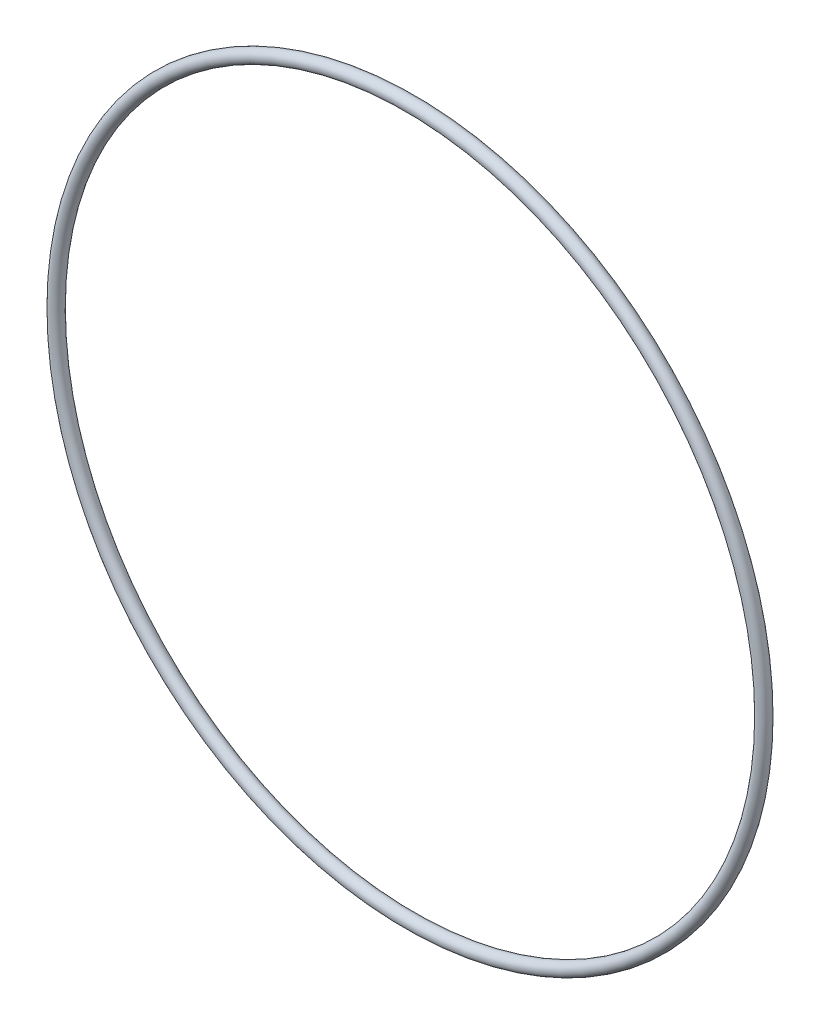
SolidWorks part; units mm, degrees
ref_plane "Front Plane" through (0, 0, 0) normal (0, 0, 1) x (1, 0, 0)
ref_plane "Top Plane" through (0, 0, 0) normal (0, 1, 0) x (1, 0, 0)
ref_plane "Right Plane" through (0, 0, 0) normal (1, 0, 0) x (0, 0, -1)
sketch "Sketch1" plane through (0, 0, 0) normal (0, 0, 1) x (1, 0, 0)
  line L0 (-49.2633, 0) -> (49.2633, 0) construction
  line L1 (-47.4853, 0) -> (47.4853, 0) construction
  line L2 (-34.8344, 34.8344) -> (34.8344, -34.8344) construction
  point P3 (47.4853, 0)
  point P4 (0, 0)
  point P8 (0, 0)
  point P9 (0, 0)
  point P10 (-49.2633, 0)
  point P11 (-47.4853, 0)
  point P14 (0, 0)
  point P15 (34.8344, -34.8344)
  point P16 (49.2633, 0)
  dimension "Actual OD" = 98.5266
  dimension "Actual ID" = 94.9706
  dimension "Actual Width" = 1.778
  dimension "D1" = 45
sketch "Sketch2" plane through (0, 0, 0) normal (0, 1, 0) x (1, 0, 0)
  line L0 (-49.2633, 0) -> (49.2633, 0) construction
  line L1 (-48.3743, 0.889) -> (-48.3743, -0.889) construction
  line L2 (0, -0.889) -> (0, 0.889) construction
  circle A0 centre (-48.3743, 0) radius 0.889
  point P12 (0, 0)
revolve "Revolve1" add sketch "Sketch2" angle 360 about L2
sketch "Sketch3" plane through (0, 0, 0) normal (1, 0, 0) x (0, 0, -1)
  line L0 (-0.889, 0) -> (0.889, 0) construction
  line L1 (-0.889, -35.614) -> (-0.889, 35.614) construction
  point P4 (0, 0)
  point P7 (-0.889, 0)
  point P9 (-0.889, -35.614)
  dimension "D1" = 1.778
  dimension "D2" = 71.2279
ref_axis "Axis1" through (0, 0, -0.9779) along (0, 0, 1)
equation "\"D1@Sketch3\"=\"Actual Width@Sketch1\""
equation "\"D2@Sketch3\"=\"Actual ID@Sketch1\"*.75"
